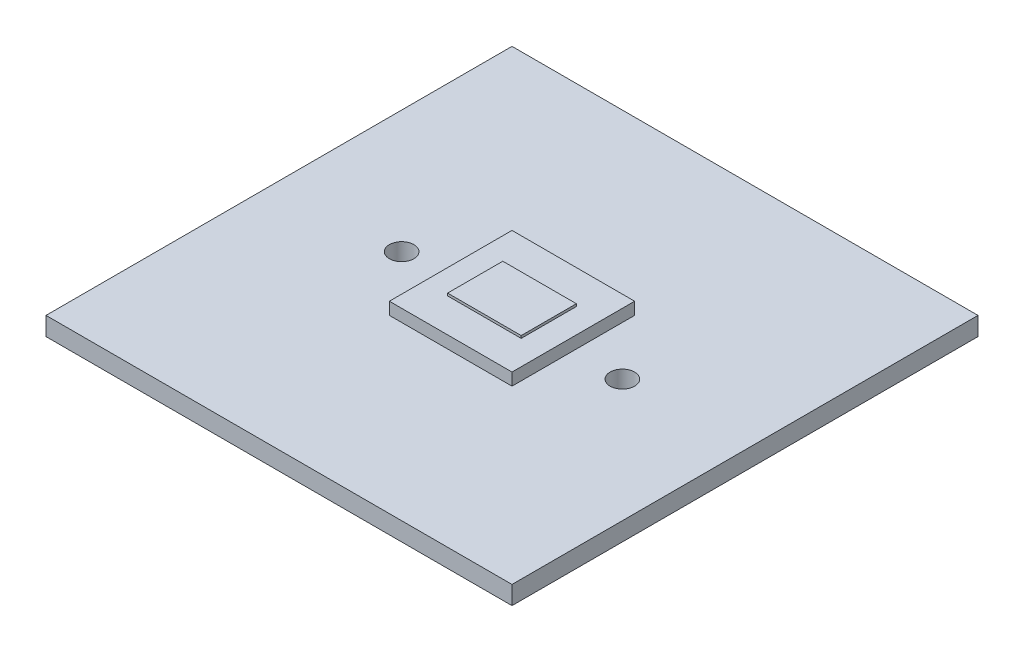
SolidWorks part; units mm, degrees
ref_plane "前视基准面" through (0, 0, 0) normal (0, 0, 1) x (1, 0, 0)
ref_plane "上视基准面" through (0, 0, 0) normal (0, 1, 0) x (1, 0, 0)
ref_plane "右视基准面" through (0, 0, 0) normal (1, 0, 0) x (0, 0, -1)
sketch "草图1" plane through (0, 0, 0) normal (0, 1, 0) x (1, 0, 0)
  line L1 (-5, -5) -> (5, -5)
  line L2 (-5, -5) -> (-5, 5)
  line L3 (-5, 5) -> (5, 5)
  line L4 (5, -5) -> (5, 5)
  line L5 (-5, -5) -> (5, 5) construction
  line L6 (-5, 5) -> (5, -5) construction
  point P0 (0, 0)
  dimension "D1" = 10
  dimension "D2" = 10
extrude "凸台-拉伸1" add sketch "草图1" along normal blind 1
sketch "草图2" plane through (0, 1, 0) normal (0, 1, 0) x (1, 0, 0)
  line L1 (-3, -2.25) -> (3, -2.25)
  line L2 (-3, -2.25) -> (-3, 2.25)
  line L3 (-3, 2.25) -> (3, 2.25)
  line L4 (3, -2.25) -> (3, 2.25)
  line L5 (-3, -2.25) -> (3, 2.25) construction
  line L6 (-3, 2.25) -> (3, -2.25) construction
  point P0 (0, 0)
  dimension "D1" = 6
  dimension "D2" = 4.5
extrude "凸台-拉伸2" add sketch "草图2" along normal blind 0.2
sketch "草图3" plane through (0, 0, 0) normal (0, -1, 0) x (1, 0, 0)
  line L1 (-19, 19) -> (19, 19)
  line L2 (-19, 19) -> (-19, -19)
  line L3 (-19, -19) -> (19, -19)
  line L4 (19, 19) -> (19, -19)
  line L5 (-19, 19) -> (19, -19) construction
  line L6 (-19, -19) -> (19, 19) construction
  point P0 (0, 0)
  dimension "D1" = 38
  dimension "D2" = 38
extrude "凸台-拉伸3" add sketch "草图3" along normal blind 1.5
sketch "草图4" plane through (0, 0, 0) normal (0, 1, 0) x (1, 0, 0)
  line L0 (5, -5) -> (5, 5) construction
  line L1 (-5, 5) -> (-5, -5) construction
  circle A0 centre (9, 0) radius 1
  circle A1 centre (-9, 0) radius 1
  dimension "D1" = 4
  dimension "D2" = 4
extrude "切除-拉伸2" cut sketch "草图4" against normal through all
ref_axis "基准轴1" through (0, 0, 0) along (0, 1, 0)
